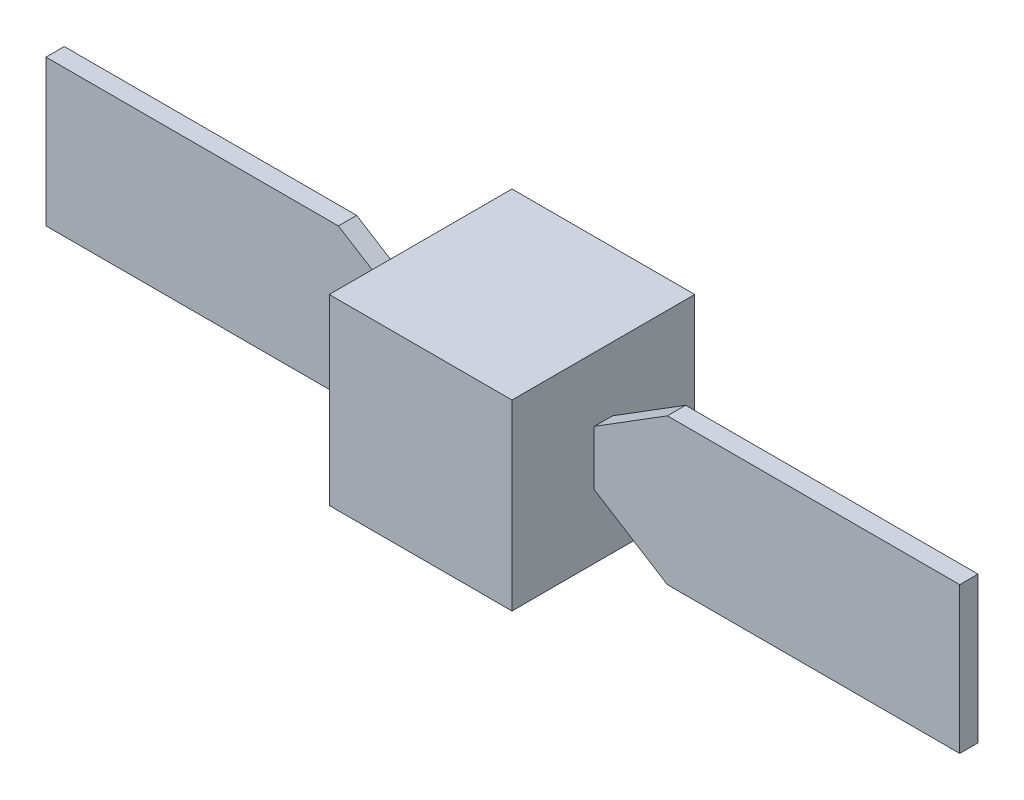
SolidWorks part; units mm, degrees
ref_plane "前视基准面" through (0, 0, 0) normal (0, 0, 1) x (1, 0, 0)
ref_plane "上视基准面" through (0, 0, 0) normal (0, 1, 0) x (1, 0, 0)
ref_plane "右视基准面" through (0, 0, 0) normal (1, 0, 0) x (0, 0, -1)
sketch "草图1" plane through (0, 0, 0) normal (0, 0, 1) x (1, 0, 0)
  line L0 (0, 0) -> (-50, 0) construction
  line L1 (0, 0) -> (50, 0) construction
  line L2 (0, 0) -> (0, 50) construction
  line L3 (0, 0) -> (0, -50) construction
  line L4 (50, 15) -> (80.9285, 15) construction
  line L5 (-50, -50) -> (50, -50)
  line L6 (-50, -50) -> (-50, 50)
  line L7 (-50, 50) -> (50, 50)
  line L8 (50, -50) -> (50, 50)
  line L9 (0, 50) -> (0, -50) construction
  line L10 (-50, 0) -> (50, 0) construction
  line L11 (50, -15) -> (80.9285, -15) construction
  line L12 (-50, -15) -> (-76.6176, -15) construction
  line L13 (-90, 40) -> (119.0856, 40) construction
  line L14 (-50, 15) -> (-81.5356, 15) construction
  line L15 (-90.015, -40) -> (118.068, -40) construction
  line L16 (90, 74.1362) -> (90, -88.2788) construction
  line L17 (-90, 72.1416) -> (-90, -88.2788) construction
  line L18 (250, 88.5304) -> (250, -117.849) construction
  line L19 (-250, 77.8749) -> (-250, -98.501) construction
  line L20 (-50, 15) -> (-90, 40)
  line L21 (-90, 40) -> (-250, 40)
  line L22 (-250, 40) -> (-250, -40)
  line L23 (-250, -40) -> (-90.015, -40)
  line L24 (-90.015, -40) -> (-50, -15)
  line L25 (-50, -15) -> (-50, 15)
  line L26 (50, 15) -> (90, 40)
  line L27 (90, 40) -> (250, 40)
  line L28 (250, 40) -> (250, -40)
  line L29 (250, -40) -> (90, -40)
  line L30 (90, -40) -> (50, -15)
  line L31 (50, -15) -> (50, 15)
  point P7 (0, 0)
  dimension "D1" = 50
  dimension "D2" = 50
  dimension "D3" = 50
  dimension "D4" = 50
  dimension "D5" = 15
  dimension "D6" = 15
  dimension "D7" = 40
  dimension "D8" = 40
  dimension "D9" = 40
  dimension "D10" = 40
  dimension "D11" = 200
  dimension "D12" = 200
extrude "凸台-拉伸1" add sketch "草图1" along normal mid plane 100 contours L5 L8 L7 L6 region at (0, 0, 0)
extrude "凸台-拉伸2" add sketch "草图1<3>" along normal mid plane 10 contours L23 L24 L6 L20 L21 L22 | L30 L29 L28 L27 L26 L8 region at (-155.7788, 0.0004, 0) region at (155.7778, 0, 0)
sketch "草图1<3>" plane through (0, 0, 0) normal (0, 0, 1) x (1, 0, 0) same geometry as "草图1"
ref_plane "基准面1" through (0, 0, -50) normal (0, 0, -1) x (-1, 0, 0)
